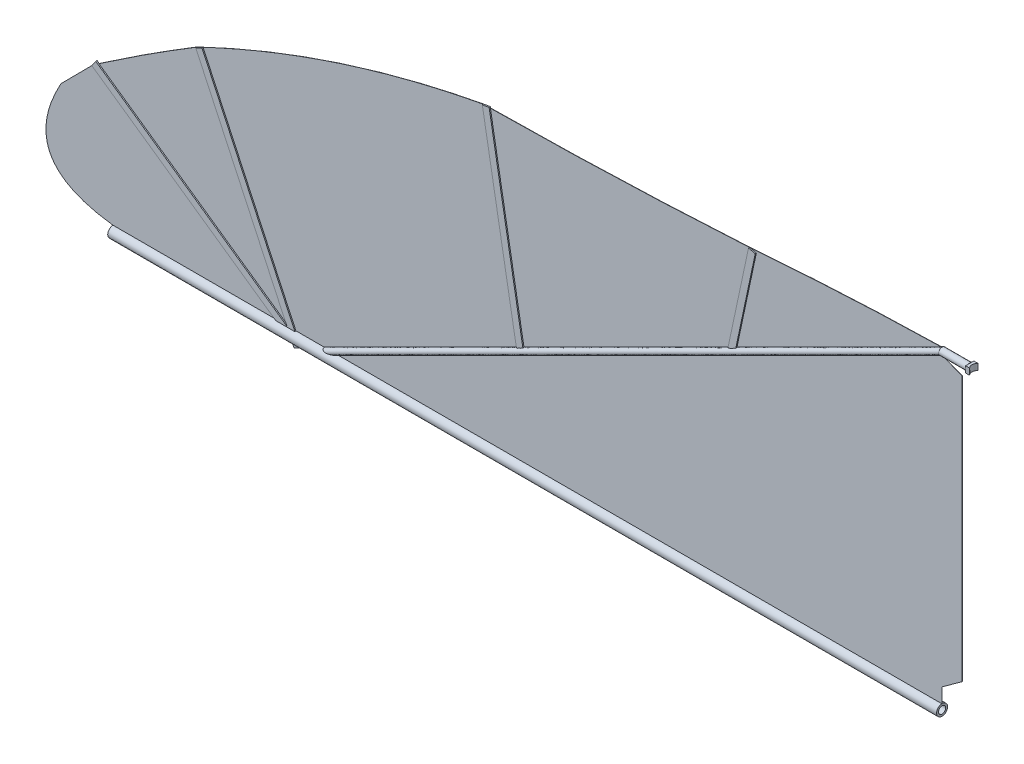
SolidWorks part; units mm, degrees
ref_plane "Front Plane" through (0, 0, 0) normal (0, 0, 1) x (1, 0, 0)
ref_plane "Top Plane" through (0, 0, 0) normal (0, 1, 0) x (1, 0, 0)
ref_plane "Right Plane" through (0, 0, 0) normal (1, 0, 0) x (0, 0, -1)
sketch "Sketch1" plane through (0, 0, 0) normal (0, 0, 1) x (1, 0, 0)
  line L0 (-300, 0) -> (300, 0)
  dimension "D1" = 600
  dimension "D2" = 300
ref_plane "Plane1" through (-300, 0, 0) normal (1, 0, 0) x (0, 0, -1)
sketch "Sketch2" plane through (-300, 0, 0) normal (1, 0, 0) x (0, 0, -1)
  circle A0 centre (0, 0) radius 4
  circle A1 centre (0, 0) radius 2.6
  dimension "D1" = 8
sweep "Sweep1" add profiles "Sketch2" path "Sketch1"
sketch "Sketch3" plane through (0, 0, 0) normal (0, 0, 1) x (1, 0, 0)
  line L0 (-150, 0) -> (300, 225)
  line L1 (-300, -2.75) -> (-300, 2.75) construction
  dimension "D1" = 150
  dimension "D2" = 225
  dimension "D3" = 300
ref_plane "Plane2" through (300, 0, 0) normal (1, 0, 0) x (0, 0, -1)
sketch "Sketch4" plane through (300, 0, 0) normal (1, 0, 0) x (0, 0, -1)
  circle A0 centre (0, 225) radius 2.5
  dimension "D1" = 5
sweep "Sweep2" add profiles "Sketch4" path "Sketch3"
sketch "Sketch5" plane through (0, 0, 0) normal (0, 0, 1) x (1, 0, 0)
  line L0 (-167.1016, -6.0508) -> (-314.5489, 97.193)
  line L1 (300, 227.5) -> (-147, 4) construction
  line L2 (-168.1505, -6.5753) -> (-239.2975, 146)
  line L3 (300, 227.5) -> (-147, 4) construction
  line L4 (-7.1438, 73.9281) -> (-31.8296, 213.9281)
  line L5 (300, 227.5) -> (-147, 4) construction
  line L6 (145.9831, 150.4915) -> (160.8621, 220.4915)
  line L7 (300, 227.5) -> (-147, 4) construction
  line L8 (-147, 4) -> (-300, 4) construction
  line L9 (-300, -4) -> (300, -4) construction
  line L10 (-300, -2.75) -> (-300, 2.75) construction
  line L11 (300, -2.75) -> (300, 2.75) construction
  line L12 (145.9831, 150.4915) -> (300, 227.5)
  line L13 (-167.1016, -6.0508) -> (145.9831, 150.4915)
  line L14 (-167.1016, -6.0508) -> (-147, 4)
  line L15 (-147, 4) -> (-300, 4)
  line L16 (-167.1016, -6.0508) -> (-168.1505, -6.5753)
  line L17 (-168.1505, -6.5753) -> (-7.1438, 73.9281)
  line L18 (-167.1016, -6.0508) -> (-168.1505, -6.5753)
  line L19 (-7.1438, 73.9281) -> (145.9831, 150.4915)
  line L20 (-7.1438, 73.9281) -> (145.9831, 150.4915)
  line L21 (300, 4) -> (300, 227.5)
  line L22 (300, 4) -> (-137, 4) construction
  line L23 (300, 4) -> (300, 222.5)
  line L24 (300, 222.5) -> (-137, 4)
  line L25 (-137, 4) -> (300, 222.5) construction
  line L26 (300, 4) -> (-137, 4) construction
  line L27 (-137, 4) -> (300, 4)
  spline S0 degree 2 poles (-300, 4) (-371.4763, 12.6094) (-337.6323, 73.9281) knots 0 0 0 1 1 1
  spline S1 degree 1 poles (-314.5489, 97.193) (-337.6323, 73.9281) knots 0 0 1 1
  spline S2 degree 2 poles (-314.5489, 97.193) (-277.6251, 122.6808) (-239.2975, 146) knots 0 0 0 1 1 1
  spline S3 degree 2 poles (-239.2975, 146) (-140.1601, 193.7292) (-31.8296, 213.9281) knots 0 0 0 1 1 1
  spline S4 degree 2 poles (-31.8296, 213.9281) (64.594, 214.756) (160.8621, 220.4915) knots 0 0 0 1 1 1
  spline S5 degree 2 poles (160.8621, 220.4915) (230.3268, 226.0245) (300, 227.5) knots 0 0 0 1 1 1
  dimension "D1" = 35
  dimension "D2" = 30
  dimension "D3" = 15
  dimension "D4" = 22
  dimension "D5" = 180
  dimension "D6" = 150
  dimension "D7" = 140
  dimension "D8" = 70
extrude "Boss-Extrude1" add sketch "Sketch5" along normal blind 0.2 separate body contours L0 S1 S0 L15 L14 | S2 L0 L13 L2 | S3 L2 L13 L4 | S4 L4 L13 L6 | S5 L6 L12 region at (-115.8204, 111.1056, 0) region at (-285.0957, 38.2925, 0) region at (-241.4728, 80.1037, 0) region at (56.0199, 163.4749, 0) region at (202.8219, 199.9727, 0)
extrude "Extrude-Thin1" add sketch "Sketch5<3>" along normal blind 1 thin contours L0 | L2 | L4 | L6 thin type one direction wall 5
sketch "Sketch5<3>" plane through (0, 0, 0) normal (0, 0, 1) x (1, 0, 0) same geometry as "Sketch5"
sketch "Sketch6" plane through (0, 0, 0) normal (0, 0, 1) x (1, 0, 0)
  line L0 (300, 4) -> (300, 222.5)
  line L1 (300, 4) -> (-137, 4) construction
  line L2 (-137, 4) -> (300, 222.5) construction
  line L3 (300, 4) -> (-137, 4)
  line L4 (-137, 4) -> (300, 222.5)
extrude "Boss-Extrude5" add sketch "Sketch6" along normal blind 0.2 separate body
sketch "Sketch8" plane through (0, 0, 0) normal (0, 0, 1) x (1, 0, 0)
  line L0 (300, 222.5) -> (314.6735, 216.9812)
  line L1 (300, 222.5) -> (-137, 4) construction
  line L4 (300, 4) -> (300, 222.5) construction
  line L6 (314.6735, 216.9812) -> (314.6735, 25.1507)
  line L7 (314.6735, 25.1507) -> (300, 14.5139)
  line L8 (300, 14.5139) -> (300, 227.5)
extrude "Boss-Extrude8" add sketch "Sketch8" along normal blind 0.2 contours L8 L7 L6 L0 region at (307.2379, 119.7692, 0)
ref_plane "Plane3" through (400, 0, 0) normal (1, 0, 0) x (0, 0, -1)
sketch "Sketch9" plane through (300, 0, 0) normal (1, 0, 0) x (0, 0, -1)
  circle A0 centre (0, 225) radius 2.5
extrude "Boss-Extrude9" add sketch "Sketch9" along normal blind 20
sketch "Sketch13" plane through (320, 0, 0) normal (1, 0, 0) x (0, 0, -1)
  line L1 (-3, 222.7235) -> (3, 222.7235)
  line L2 (-3, 222.7235) -> (-3, 227.2765)
  line L3 (-3, 227.2765) -> (3, 227.2765)
  line L4 (3, 222.7235) -> (3, 227.2765)
  line L5 (-3, 222.7235) -> (3, 227.2765) construction
  line L6 (-3, 227.2765) -> (3, 222.7235) construction
  circle A0 centre (0, 225) radius 2.5 construction
  point P0 (0, 225)
  dimension "D1" = 6
extrude "Boss-Extrude11" add sketch "Sketch13" along normal blind 3
sketch "Sketch14" plane through (0, 222.7235, 0) normal (0, -1, 0) x (1, 0, 0)
  line L6 (320, 3) -> (320, 1.0333)
  line L7 (320, 1.0333) -> (320, -1.0333)
  line L8 (320, -1.0333) -> (320, -3)
  line L9 (320, -3) -> (323, -3)
  line L10 (323, -3) -> (323, 3)
  line L11 (323, 3) -> (320, 3)
  line L12 (320, 3) -> (320, 1.0333)
  line L13 (320, 1.0333) -> (320, -1.0333)
  line L14 (320, -1.0333) -> (320, -3)
  line L15 (320, -3) -> (323, -3)
  line L16 (323, -3) -> (323, 3)
  line L17 (323, 3) -> (320, 3)
  arc A0 (323, 3) -> (323, -3) centre (325.6458, 0) ccw
  line M11 (323, -3) -> (323, 3)
  dimension "D1" = 4
  dimension "D2" = 0
extrude "Cut-Extrude2" cut sketch "Sketch14" against normal blind 22 contours A0 M11 region at (322.4496, 222.7235, 0)
